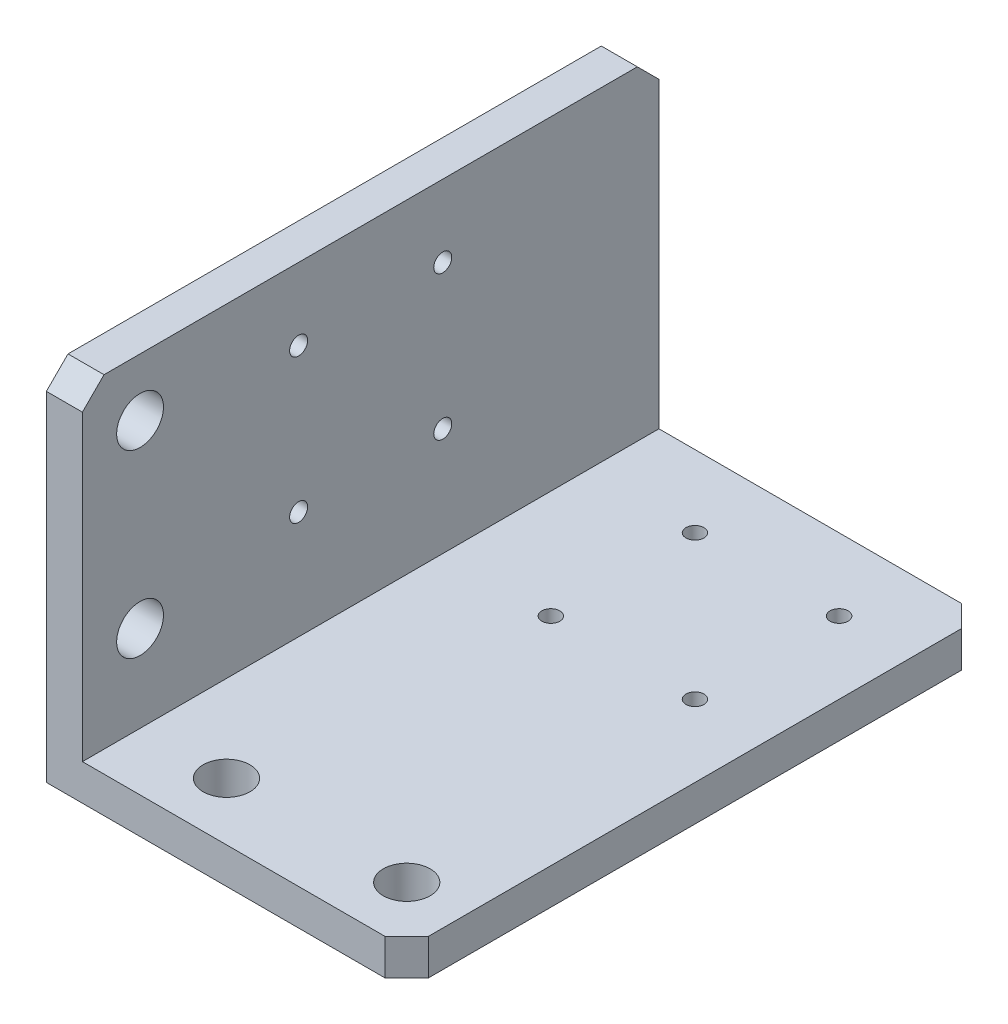
SolidWorks part; units mm, degrees
material "Lega 1060"
ref_plane "Piano frontale" through (0, 0, 0) normal (0, 0, 1) x (1, 0, 0)
ref_plane "Piano superiore" through (0, 0, 0) normal (0, 1, 0) x (1, 0, 0)
ref_plane "Piano destro" through (0, 0, 0) normal (1, 0, 0) x (0, 0, -1)
sketch "Schizzo1" plane through (0, 0, 0) normal (0, 0, 1) x (1, 0, 0)
  line L0 (0, 0) -> (0, 50)
  line L1 (0, 50) -> (5, 50)
  line L2 (5, 50) -> (5, 5)
  line L3 (5, 5) -> (50, 5)
  line L4 (50, 5) -> (50, 0)
  line L5 (50, 0) -> (0, 0)
  dimension "D1" = 5
  dimension "D2" = 5
  dimension "D3" = 50
  dimension "D4" = 50
extrude "Estrusione-Estrusione1" add sketch "Schizzo1" along normal blind 80
sketch "Schizzo2" plane through (0, 0, 0) normal (0, -1, 0) x (1, 0, 0)
  line L0 (5.4524, 72) -> (42.7933, 72) construction
  line L1 (0, 80) -> (50, 80) construction
  line L5 (50, 80) -> (50, 0) construction
  point P4 (17, 72)
  point P5 (42, 72)
  dimension "D1" = 8
  dimension "D2" = 25
  dimension "D3" = 8
sketch "Schizzo3" plane through (0, 0, 0) normal (-1, 0, 0) x (0, 0, 1)
  line L0 (72, 44.621) -> (72, 5.772) construction
  line L1 (80, 50) -> (80, 0) construction
  line L2 (80, 50) -> (0, 50) construction
  point P4 (72, 42)
  point P5 (72, 17)
  dimension "D1" = 8
  dimension "D2" = 8
  dimension "D3" = 25
hole_wizard "Foro Ø6.5 (6.5)-1" positions "Schizzo5" profile "Schizzo4" hole size "Ø6.5" standard "ISO" end condition through all
sketch "Schizzo5" plane through (0, 0, 0) normal (0, -1, 0) x (-1, 0, 0)
  point P0 (-17, -72)
  point P3 (-42, -72)
sketch "Schizzo4" plane through (17, 0, 72) normal (1, 0, 0) x (0, 0, -1)
  line L0 (0, 0) -> (0, 50)
  line L1 (0, 50) -> (3.25, 50)
  line L2 (3.25, 50) -> (3.25, 0)
  line L5 (3.25, 0) -> (0, 0)
  line L11 (0, -6.35) -> (0, 107.95) construction
  dimension "Thru Hole Dia." = 6.5
  dimension "Thru Hole Depth" = 50
hole_wizard "Foro Ø6.5 (6.5)-2" positions "Schizzo7" profile "Schizzo6" hole size "Ø6.5" standard "ISO"
sketch "Schizzo7" plane through (0, 0, 0) normal (-1, 0, 0) x (0, 0, 1)
  point P1 (72, 42)
  point P4 (72, 17)
sketch "Schizzo6" plane through (0, 42, 72) normal (0, 1, 0) x (0, 0, 1)
  line L0 (0, 0) -> (0, 6.9528)
  line L1 (0, 6.9528) -> (3.25, 5)
  line L2 (3.25, 5) -> (3.25, 0)
  line L5 (3.25, 0) -> (0, 0)
  line L10 (0, 6.9528) -> (-3.25, 5) construction
  line L11 (0, -6.35) -> (0, 107.95) construction
  dimension "Hole Dia." = 6.5
  dimension "Hole Depth" = 5
  dimension "Drill Angle" = 118
ref_plane "Piano1" through (0, 0, 40) normal (0, 0, 1) x (1, 0, 0)
sketch "Schizzo8" plane through (0, 0, 0) normal (0, -1, 0) x (1, 0, 0)
  line L0 (30, 20) -> (7.0316, 20) construction
  line L1 (30, 20) -> (22.8949, 12.8949) construction
  line L2 (0, 80) -> (50, 80) construction
  line L3 (50, 80) -> (50, 0) construction
  circle A0 centre (20, 10) radius 1.75
  circle A1 centre (20, 30) radius 1.75
  circle A2 centre (40, 30) radius 1.75
  circle A3 centre (40, 10) radius 1.75
  point P18 (30, 20)
  dimension "D3" = 3.5
  dimension "D1" = 60
  dimension "D2" = 20
  dimension "D4" = 45
  dimension "D5" = 20
  dimension "D6" = 4
sketch "Schizzo9" plane through (0, 0, 0) normal (-1, 0, 0) x (0, 0, 1)
  line L0 (40, 44.574) -> (40, 30) construction
  line L1 (40, 30) -> (33.014, 36.986) construction
  line L2 (80, 50) -> (0, 50) construction
  line L3 (80, 50) -> (80, 0) construction
  circle A0 centre (30, 40) radius 1.75
  circle A1 centre (50, 40) radius 1.75
  circle A2 centre (50, 20) radius 1.75
  circle A3 centre (30, 20) radius 1.75
  point P18 (40, 30)
  dimension "D4" = 3.5
  dimension "D1" = 20
  dimension "D2" = 40
  dimension "D3" = 45
  dimension "D5" = 20
  dimension "D6" = 4
chamfer "Smusso1" distance 3 angle 45 4 edges at (2.5, 50, 0) (50, 2.5, 0) (50, 2.5, 80) (2.5, 50, 80)
hole_wizard "M3 Tapped Hole1" positions "3DSketch1" profile "Sketch1" tap size "M3" standard "ISO" end condition through all
sketch3d "3DSketch1"
  point P0 (20, 0, 30)
  point P3 (40, 0, 30)
  point P6 (40, 0, 10)
  point P9 (20, 0, 10)
sketch "Sketch1" plane through (20, 0, 30) normal (1, 0, 0) x (0, 0, -1)
  line L0 (0, 0) -> (0, 50)
  line L1 (0, 50) -> (1.25, 50)
  line L2 (1.25, 50) -> (1.25, 0)
  line L5 (1.25, 0) -> (0, 0)
  line L11 (0, -6.35) -> (0, 107.95) construction
  dimension "Thru Tap Drill Dia." = 2.5
  dimension "Thru Tap Drill Depth" = 50
cosmetic thread "Cosmetic Thread1" parameters "D2"=3
cosmetic thread "Cosmetic Thread2" parameters "D2"=3
cosmetic thread "Cosmetic Thread3" parameters "D2"=3
cosmetic thread "Cosmetic Thread4" parameters "D2"=3
hole_wizard "M3 Tapped Hole2" positions "3DSketch2" profile "Sketch2" tap size "M3" standard "ISO" end condition through all
sketch3d "3DSketch2"
  point P0 (0, 40, 30)
  point P3 (0, 40, 50)
  point P6 (0, 20, 50)
  point P9 (0, 20, 30)
sketch "Sketch2" plane through (0, 40, 30) normal (0, 1, 0) x (0, 0, 1)
  line L0 (0, 0) -> (0, 50)
  line L1 (0, 50) -> (1.25, 50)
  line L2 (1.25, 50) -> (1.25, 0)
  line L5 (1.25, 0) -> (0, 0)
  line L11 (0, -6.35) -> (0, 107.95) construction
  dimension "Thru Tap Drill Dia." = 2.5
  dimension "Thru Tap Drill Depth" = 50
cosmetic thread "Cosmetic Thread5" parameters "D2"=3
cosmetic thread "Cosmetic Thread6" parameters "D2"=3
cosmetic thread "Cosmetic Thread7" parameters "D2"=3
cosmetic thread "Cosmetic Thread8" parameters "D2"=3
